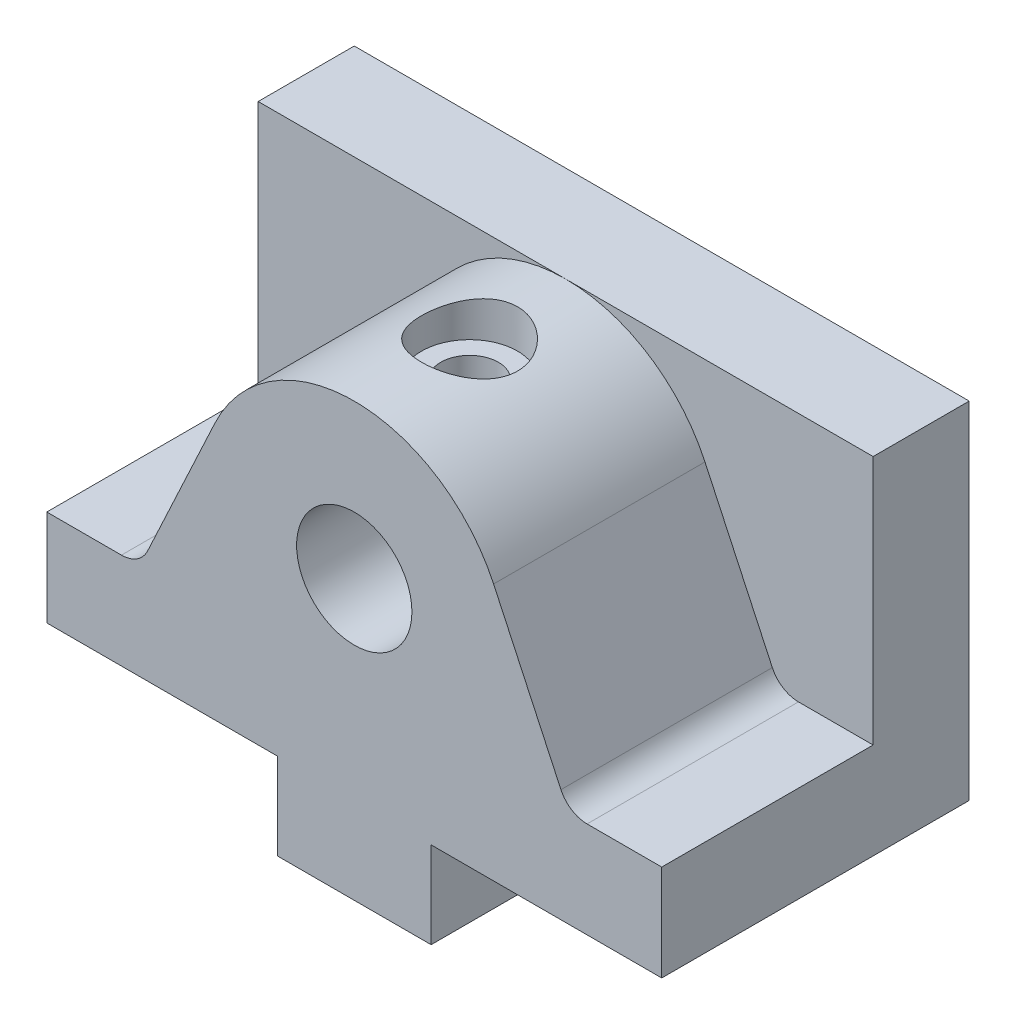
SolidWorks part; units mm, degrees
ref_plane "Front Plane" through (0, 0, 0) normal (0, 0, 1) x (1, 0, 0)
ref_plane "Top Plane" through (0, 0, 0) normal (0, 1, 0) x (1, 0, 0)
ref_plane "Right Plane" through (0, 0, 0) normal (1, 0, 0) x (0, 0, -1)
sketch "Sketch2" plane through (0, 0, 0) normal (0, 0, 1) x (1, 0, 0)
  line L0 (0, 10) -> (64, 10)
  line L1 (0, 0) -> (24, 0)
  line L2 (0, 0) -> (0, 36)
  line L3 (0, 36) -> (64, 36)
  line L4 (64, 0) -> (64, 36)
  line L5 (32, 0) -> (32, 4) construction
  line L6 (17.4991, 26.7619) -> (9.6829, 10)
  line L7 (46.5009, 26.7619) -> (56.235, 5.8871)
  line L8 (40, 0) -> (64, 0)
  line L9 (32, 10) -> (32, 36) construction
  line L10 (24, 0) -> (24, -9)
  line L11 (24, -9) -> (40, -9)
  line L12 (40, 0) -> (40, -9)
  arc A0 (46.5009, 26.7619) -> (17.4991, 26.7619) centre (32, 20) ccw
  dimension "D3" = 32
  dimension "D1" = 64
  dimension "D2" = 36
  dimension "D4" = 50
  dimension "D5" = 25
  dimension "D6" = 10
  dimension "D7" = 16
  dimension "D8" = 9
  dimension "D9" = 8
extrude "Boss-Extrude2" add sketch "Sketch2" along normal blind 22 contours L7 A0 L6 L0 | L12 L8 L4 L0 L2 L1 L10 L11 region at (32, 3.2551, 0) region at (32, 20.8247, 0)
extrude "Boss-Extrude3" add sketch "Sketch2<4>" against normal blind 10 contours A0 L3 L2 L0 L6 | A0 L7 L0 L4 L3 | L7 A0 L6 L0 | L12 L8 L4 L0 L2 L1 L10 L11 region at (8.8804, 25.0608, 0) region at (32, 3.2551, 0) region at (32, 20.8247, 0) region at (55.1196, 25.0608, 0)
sketch "Sketch2<4>" plane through (0, 0, 0) normal (0, 0, 1) x (1, 0, 0) same geometry as "Sketch2"
fillet "Fillet1" radius 3 2 edges at (9.6829, 10, 11) (54.3171, 10, 11)
sketch "Sketch3" plane through (0, 0, 22) normal (0, 0, 1) x (1, 0, 0)
  circle A0 centre (32, 20) radius 6
  dimension "D1" = 12
extrude "Cut-Extrude1" cut sketch "Sketch3" against normal blind 24
sketch "Sketch4" plane through (0, -9, 0) normal (0, -1, 0) x (1, 0, 0)
  line L0 (24, 22) -> (40, 22) construction
  line L1 (24, 22) -> (24, -10) construction
  line L2 (24, 22) -> (24, -10) construction
  circle A0 centre (32, 14) radius 3
  circle A1 centre (32, -2) radius 3
  dimension "D1" = 6
  dimension "D2" = 6
  dimension "D3" = 8
  dimension "D4" = 16
  dimension "D5" = 8
  dimension "D6" = 8
extrude "Cut-Extrude2" cut sketch "Sketch4" against normal blind 16
hole_wizard "CBORE for M12 Hex Head Bolt3" positions "Sketch16" profile "Sketch17" counterbore size "M12" standard "ANSI Metric" end condition up to next
sketch "Sketch16" plane through (0, 36, 0) normal (0, 1, 0) x (1, 0, 0)
  line L0 (0, 10) -> (64, 10) construction
  line L1 (64, -22) -> (64, 0) construction
  point P0 (32, -10)
  dimension "D1" = 20
  dimension "D2" = 32
sketch "Sketch17" plane through (32, 36, 10) normal (1, 0, 0) x (0, 0, 1)
  line L0 (0, 0) -> (0, 10)
  line L1 (0, 10) -> (3, 10)
  line L3 (3, 10) -> (3, 4)
  line L4 (3, 4) -> (5, 4)
  line L5 (5, 4) -> (5, 0)
  line L7 (5, 0) -> (0, 0)
  line L11 (0, -6.35) -> (0, 107.95) construction
  dimension "Thru Hole Dia." = 6
  dimension "Thru Hole Depth" = 10
  dimension "C'Bore Dia." = 10
  dimension "C'Bore Depth" = 4
